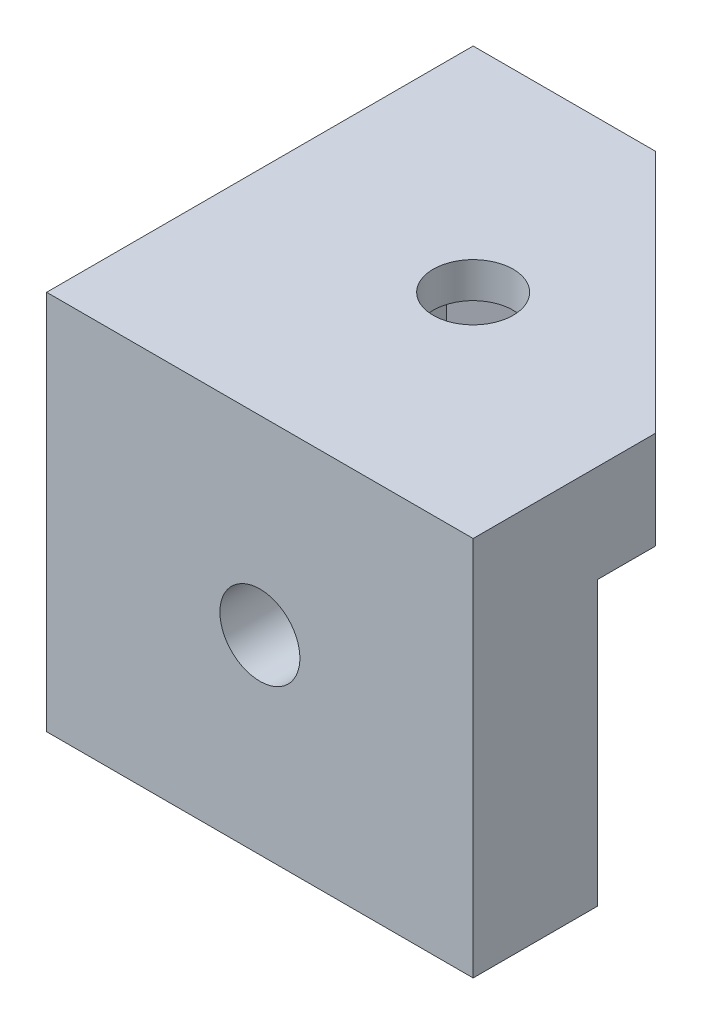
SolidWorks part; units mm, degrees
ref_plane "Front Plane" through (0, 0, 0) normal (0, 0, 1) x (1, 0, 0)
ref_plane "Top Plane" through (0, 0, 0) normal (0, 1, 0) x (1, 0, 0)
ref_plane "Right Plane" through (0, 0, 0) normal (1, 0, 0) x (0, 0, -1)
sketch "Sketch1" plane through (0, 0, 0) normal (0, 1, 0) x (1, 0, 0)
  line L1 (0, 0) -> (38.1, 0)
  line L5 (0, 0) -> (0, 38.1)
  line L6 (0, 38.1) -> (38.1, 38.1)
  line L8 (38.1, 38.1) -> (38.1, 0)
  dimension "D1" = 38.1
extrude "Main Body" add sketch "Sketch1" along normal blind 34
sketch "Sketch3" plane through (0, 0, 0) normal (0, 0, 1) x (1, 0, 0)
  line L0 (0, 0) -> (38.1, 34) construction
  circle A0 centre (19.05, 17) radius 3.5719
  circle A1 centre (19.05, 17) radius 7.9375 construction
  dimension "D1" = 7.1437
  dimension "D2" = 15.875
extrude "9/32 Right Rail" cut sketch "Sketch3" against normal blind 5.5562 and the other way through all
sketch "Sketch4" plane through (0, 0, 0) normal (-1, 0, 0) x (0, 0, 1)
  line L0 (0, 0) -> (-38.1, 34) construction
  circle A0 centre (-19.05, 17) radius 3.5719
  circle A1 centre (-19.05, 17) radius 7.9375 construction
  dimension "D1" = 7.1437
  dimension "D2" = 15.875
extrude "9/32 Left Rail" cut sketch "Sketch4" against normal blind 5.5562
sketch "Sketch8" plane through (0, 34, 0) normal (0, 1, 0) x (1, 0, 0)
  line L0 (0, 0) -> (38.1, 38.1) construction
  circle A0 centre (19.05, 19.05) radius 3.175 construction
  circle A1 centre (19.05, 19.05) radius 7.9375 construction
  circle A2 centre (19.05, 19.05) radius 3.5719
  dimension "D1" = 6.35
  dimension "D2" = 15.875
  dimension "D3" = 0.3969
extrude "9/32 Topper" cut sketch "Sketch8" against normal blind 10 and the other way through all
ref_plane "Plane1" through (5.5562, 0, 0) normal (-1, 0, 0) x (0, 0, 1)
sketch "Sketch9" plane through (0, 0, 0) normal (-1, 0, 0) x (0, 0, 1)
  line L0 (-19.05, 0) -> (-19.05, 34) construction
  line L1 (-12.6342, 17) -> (-15.8421, 22.5562) construction
  line L2 (-15.8421, 22.5562) -> (-22.2579, 22.5562) construction
  line L3 (-22.2579, 22.5562) -> (-25.4658, 17) construction
  line L4 (-25.4658, 17) -> (-22.2579, 11.4437) construction
  line L5 (-22.2579, 11.4437) -> (-15.8421, 11.4437) construction
  line L6 (-15.8421, 11.4437) -> (-12.6342, 17) construction
  line L7 (-38.1, 0) -> (0, 0) construction
  line L8 (-38.1, 34) -> (0, 34) construction
  line L9 (-22.3152, 22.6555) -> (-25.5804, 17)
  line L10 (-25.5804, 17) -> (-22.3152, 11.3445)
  line L11 (-22.3152, 11.3445) -> (-15.7848, 11.3445)
  line L12 (-15.7848, 11.3445) -> (-12.5196, 17)
  line L13 (-12.5196, 17) -> (-15.7848, 22.6555)
  line L14 (-15.7848, 22.6555) -> (-22.3152, 22.6555)
  line L15 (-38.1, 27.65) -> (-38.1, 6.35) construction
  line L16 (-38.1, 34) -> (-38.1, 0) construction
  line L17 (-38.1, 6.35) -> (-5.5562, 6.35) construction
  line L18 (-5.5562, 6.35) -> (-5.5562, 27.65) construction
  line L19 (-5.5562, 27.65) -> (-38.1, 27.65) construction
  line L20 (0, 34) -> (0, 0) construction
  circle A0 centre (-19.05, 17) radius 5.5563 construction
  point P15 (-19.05, 17)
  point P27 (-38.1, 17)
  point P29 (-38.1, 17)
  dimension "D1" = 11.1125
  dimension "D3" = 5.5562
  dimension "D4" = 6.35
  dimension "D2" = 0.0992
extrude "Hex Hole Right" cut sketch "Sketch9" against normal up to surface (38.1 mm away) from surface up to face at (38.1, 17, -19.05) starting at plane "Plane1"
ref_plane "Plane2" through (0, 0, -5.5563) normal (0, 0, 1) x (1, 0, 0)
sketch "Sketch10" plane through (0, 0, 0) normal (0, 0, 1) x (1, 0, 0)
  line L0 (19.05, 0) -> (19.05, 34) construction
  line L1 (0, 0) -> (38.1, 0) construction
  line L2 (0, 34) -> (38.1, 34) construction
  line L3 (15.7848, 22.6555) -> (12.5196, 17)
  line L4 (25.4658, 17) -> (22.2579, 22.5562) construction
  line L5 (22.2579, 22.5562) -> (15.8421, 22.5562) construction
  line L6 (15.8421, 22.5562) -> (12.6342, 17) construction
  line L13 (12.6342, 17) -> (15.8421, 11.4437) construction
  line L14 (15.8421, 11.4437) -> (22.2579, 11.4437) construction
  line L15 (22.2579, 11.4437) -> (25.4658, 17) construction
  line L16 (12.5196, 17) -> (15.7848, 11.3445)
  line L17 (15.7848, 11.3445) -> (22.3152, 11.3445)
  line L18 (22.3152, 11.3445) -> (25.5804, 17)
  line L19 (25.5804, 17) -> (22.3152, 22.6555)
  line L20 (22.3152, 22.6555) -> (15.7848, 22.6555)
  circle A0 centre (19.05, 17) radius 5.5563 construction
  dimension "D1" = 11.1125
  dimension "D2" = 0.0992
extrude "Hex Hole Left" cut sketch "Sketch10" against normal up to surface (38.1 mm away) from surface up to face at (19.05, 17, -38.1) starting at plane "Plane2"
sketch "Sketch13" plane through (0, 34, 0) normal (0, 1, 0) x (1, 0, 0)
  line L0 (22.3152, 5.5563) -> (15.7848, 5.5563) construction
  line L1 (5.5562, 15.7848) -> (5.5562, 22.3152) construction
  line L2 (38.1, 11.1125) -> (11.1125, 11.1125)
  line L3 (11.1125, 38.1) -> (11.1125, 11.1125)
  line L5 (22.3152, 5.5563) -> (15.7848, 5.5563) construction
  line L6 (5.5562, 15.7848) -> (5.5562, 22.3152) construction
  line L7 (38.1, 38.1) -> (0, 38.1) construction
  line L8 (38.1, 0) -> (38.1, 38.1) construction
  line L9 (11.1125, 38.1) -> (38.1, 38.1)
  line L10 (38.1, 38.1) -> (38.1, 11.1125)
  point P2 (8.9807, 8.9807)
  point P3 (13.3137, 13.3137)
  point P15 (10.6863, 10.6863)
  dimension "D1" = 5.5562
ref_plane "Plane4" through (0, 17, 0) normal (0, 1, 0) x (1, 0, 0)
extrude "Inner Cavity" cut sketch "Sketch13" along direction (0, -1, 0) on the side of the normal offset from surface 8.7312 and the other way up to surface (34 mm away) from surface up to face at (19.05, 34, -22.6219) other way up to face at (19.05, 0, -19.05) starting at plane "Plane4"
sketch "Sketch14" plane through (0, 34, 0) normal (0, 1, 0) x (1, 0, 0)
  line L0 (38.1, 0) -> (0, 38.1) construction
  line L1 (24.7055, 22.3152) -> (19.05, 25.5804)
  line L2 (24.6063, 22.2579) -> (19.05, 25.4658) construction
  line L3 (19.05, 25.4658) -> (13.4938, 22.2579) construction
  line L4 (13.4938, 22.2579) -> (13.4938, 15.8421) construction
  line L5 (13.4938, 15.8421) -> (19.05, 12.6342) construction
  line L6 (19.05, 12.6342) -> (24.6063, 15.8421) construction
  line L7 (24.6063, 15.8421) -> (24.6063, 22.2579) construction
  line L8 (19.05, 25.5804) -> (13.3945, 22.3152)
  line L9 (13.3945, 22.3152) -> (13.3945, 15.7848)
  line L10 (13.3945, 15.7848) -> (19.05, 12.5196)
  line L11 (19.05, 12.5196) -> (24.7055, 15.7848)
  line L12 (24.7055, 15.7848) -> (24.7055, 22.3152)
  line L14 (38.1, 38.1) -> (38.1, 11.1125) construction
  circle A0 centre (19.05, 19.05) radius 5.5562 construction
  point P18 (0, 0)
  dimension "D1" = 11.1125
  dimension "D2" = 0.0992
extrude "Hex Hole Top" cut sketch "Sketch14" along normal offset from surface (13.825 mm away) 3.175 from surface up to face at (19.05, 34, -22.6219) starting at plane "Plane4"
sketch "Sketch16" plane through (0, 34, 0) normal (0, 1, 0) x (1, 0, 0)
  line L0 (38.1, 38.1) -> (16.2767, 38.1)
  line L1 (38.1, 38.1) -> (0, 38.1) construction
  line L2 (16.2767, 38.1) -> (38.1, 16.2767)
  line L3 (38.1, 16.2767) -> (38.1, 38.1)
  line L4 (38.1, 0) -> (38.1, 38.1) construction
  circle A2 centre (19.05, 19.05) radius 3.5719 construction
  dimension "D1" = 7.9375
extrude "Top Corner" cut sketch "Sketch16" against normal up to next
